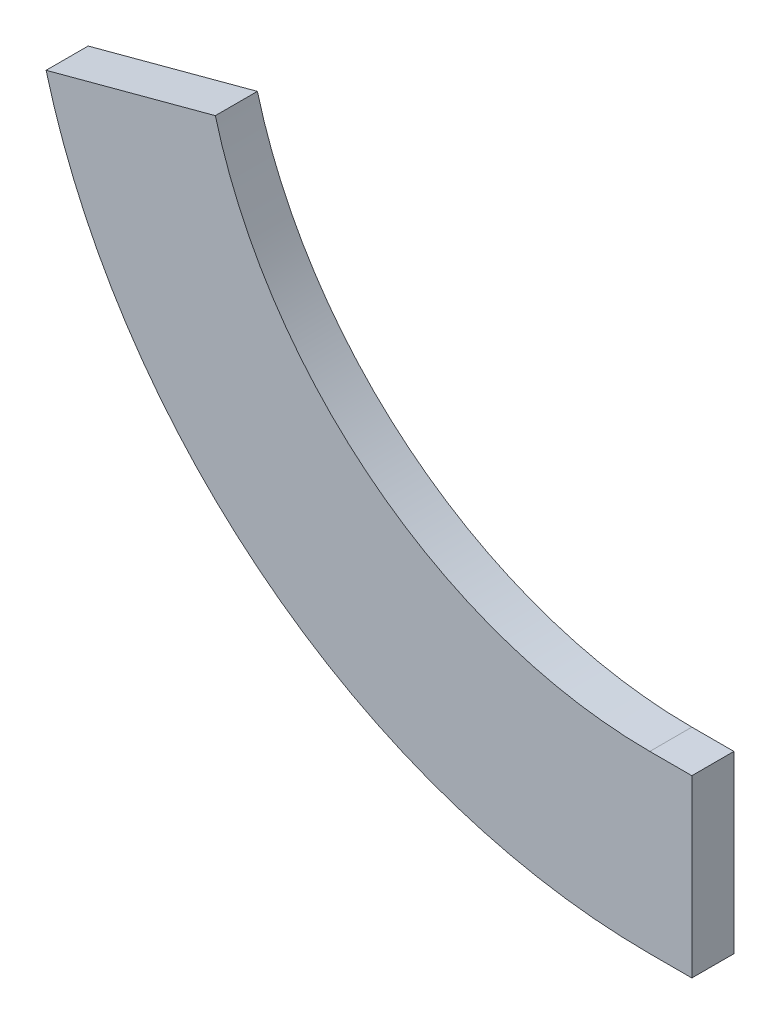
SolidWorks part; units mm, degrees
material "Plain Carbon Steel"
ref_plane "Front Plane" through (0, 0, 0) normal (0, 0, 1) x (1, 0, 0)
ref_plane "Top Plane" through (0, 0, 0) normal (0, 1, 0) x (1, 0, 0)
ref_plane "Right Plane" through (0, 0, 0) normal (1, 0, 0) x (0, 0, -1)
sketch "Sketch1" plane through (0, 0, 0) normal (0, 0, 1) x (1, 0, 0)
  line L0 (-97.4016, -31.75) -> (-100.4496, -31.75)
  line L1 (-131.9395, -7.587) -> (-144.2068, -10.874)
  line L2 (-100.4496, -44.45) -> (-97.4016, -44.45)
  line L3 (-97.4016, -44.45) -> (-97.4016, -31.75)
  line L4 (-97.4016, -44.704) -> (-97.4016, -31.496) construction
  line L5 (-97.4016, -31.496) -> (-100.4496, -31.496) construction
  line L6 (-97.4016, -44.704) -> (-100.4496, -44.704) construction
  line L7 (-100.4496, -71.9043) -> (-100.4496, -44.704) construction
  line L9 (-107.155, -0.946) -> (3231.9626, 893.7679) construction
  line L10 (-100.4496, -31.496) -> (-100.4496, -2.54) construction
  arc A0 (-100.4496, -31.75) -> (-131.9395, -7.587) centre (-100.4496, 0.8507) cw
  arc A1 (-144.2068, -10.874) -> (-100.4496, -44.45) centre (-100.4496, 0.8507) ccw
  point P14 (-76.3376, -35.8006)
  point P17 (-135.3431, -28.2666)
  dimension "D1" = 0.254
  dimension "D2" = 0.254
  dimension "D3" = 12.7
  dimension "D4" = 75
extrude "Boss-Extrude1" add sketch "Sketch1" along normal mid plane 3.048 contours A0 L1 A1 L2 L3 L0
